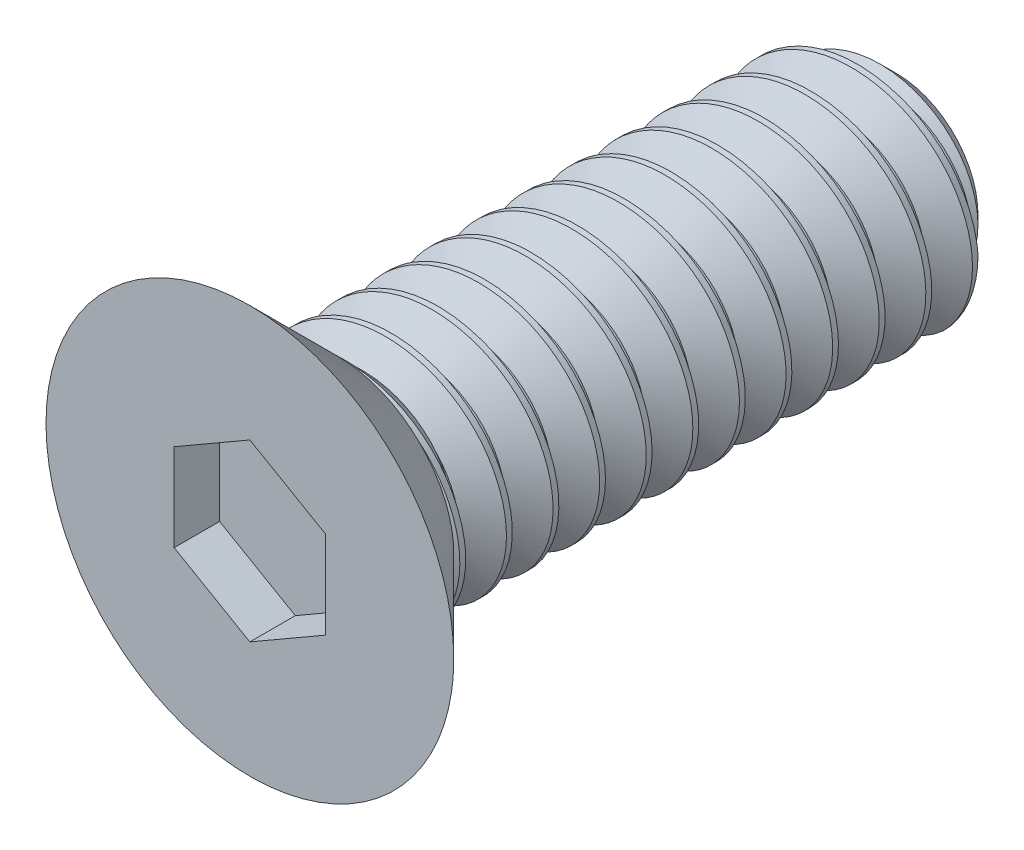
SolidWorks part; units mm, degrees
material "AISI Type 316L stainless steel"
ref_plane "Front" through (0, 0, 0) normal (0, 0, 1) x (1, 0, 0)
ref_plane "Top" through (0, 0, 0) normal (0, 1, 0) x (1, 0, 0)
ref_plane "Right" through (0, 0, 0) normal (1, 0, 0) x (0, 0, -1)
sketch "Sketch1" plane through (0, 0, 0) normal (1, 0, 0) x (0, 0, -1)
  line L0 (0, 2) -> (0.2, 2) construction
  line L1 (0.2, 2) -> (1.2, 1) construction
  line L2 (0, 1) -> (6, 1)
  line L3 (6, 1) -> (6, 0)
  line L4 (6, 0) -> (0, 0)
  line L5 (0, 0) -> (0, 2) construction
  line L6 (0, 2) -> (0, -2) construction
  line L7 (6, 1) -> (6, -1) construction
  line L8 (0, -2) -> (0.2, -2) construction
  line L9 (0.2, -2) -> (1.2, -1) construction
  line L11 (0, 1) -> (0, 0)
  line L12 (1.2, 1) -> (1.2, 0) construction
revolve "Revolve1" add sketch "Sketch1" angle 360 mid plane about L4
sketch "Sketch3" plane through (0, 0, -6) normal (0, 0, -1) x (-1, 0, 0)
  circle A0 centre (0, 0) radius 1
curve "Helix/Spiral1" pitch 0.4 height 6 radius 1 centre (0, 0, -6) axis (0, 0, 1) start towards (0, 1, 0)
sketch "Sketch2" plane through (0, 0, 0) normal (1, 0, 0) x (0, 0, -1)
  line L0 (6, 1) -> (6.35, 1)
  line L1 (6.35, 1) -> (6.2, 0.7402)
  line L2 (6.2, 0.7402) -> (6.15, 0.7402)
  line L3 (6.15, 0.7402) -> (6, 1)
  line L4 (6.075, 0.8701) -> (6.275, 0.8701) construction
  dimension "D1" = 60
  dimension "D2" = 0.05
  dimension "D3" = 0.2
chamfer "Chamfer1" distance 0.3 angle 45 1 edges at (0, 1, -6)
sweep "Cut-Sweep1" cut profiles "Sketch2" path "Helix/Spiral1" align with end faces yes
sketch "Sketch7" plane through (0, 0, 0) normal (1, 0, 0) x (0, 0, -1)
  line L0 (0, 2) -> (0.2, 2) construction
  line L1 (0.2, 2) -> (1.2, 1) construction
  line L2 (0, 2) -> (0.2, 2)
  line L3 (0.2, 2) -> (1.2, 1)
  line L4 (1.2, 1) -> (1.2, 0) construction
  line L5 (1.2, 1) -> (1.2, 0)
  line L7 (0, 0) -> (0, 2) construction
  line L8 (0, 0) -> (0, 2)
  line L9 (0, 0) -> (1.2, 0)
  line L10 (2.2, 0) -> (-2.2, 0) construction
revolve "Revolve2" add sketch "Sketch7" angle 360 mid plane about L9
ref_plane "Plane1" through (0, 0, -1.2) normal (0, 0, 1) x (1, 0, 0)
sketch "Sketch8" plane through (0, 0, -1.2) normal (0, 0, 1) x (1, 0, 0)
  circle A0 centre (0, 0) radius 1
extrude "Boss-Extrude1" add sketch "Sketch8" against normal through all draft 45
sketch "Sketch5" plane through (0, 0, 0) normal (0, 0, 1) x (1, 0, 0)
  line L1 (0.65, -0.3753) -> (0.65, 0.3753)
  line L2 (0.65, 0.3753) -> (0, 0.7506)
  line L3 (0, 0.7506) -> (-0.65, 0.3753)
  line L4 (-0.65, 0.3753) -> (-0.65, -0.3753)
  line L5 (-0.65, -0.3753) -> (0, -0.7506)
  line L6 (0, -0.7506) -> (0.65, -0.3753)
  circle A0 centre (0, 0) radius 0.65 construction
  dimension "Hex" = 1.3
extrude "Cut-Extrude2" cut sketch "Sketch5" against normal blind 0.84
sketch "Sketch6" plane through (0, 0, 0) normal (0, 0, 1) x (1, 0, 0)
  circle A0 centre (0, 0) radius 0.7506
extrude "Cut-Extrude3" cut sketch "Sketch6" against normal blind 0.84 draft 45
sketch "Sketch9" [suppressed] plane through (0, 0, -5.5) normal (0, 0, 1) x (1, 0, 0)
  circle A1 centre (0, 0) radius 5
  circle A2 centre (0, 0) radius 5
  point P0 (0, 5)
  dimension "D1" = 0
extrude "Boss-Extrude2" [suppressed] add sketch "Sketch9" against normal offset from surface (18.5 mm away) 26 up to face at (0, 0.7, -6)
fillet "Fillet1" [suppressed] radius 0.2
sketch "Sketch10" plane through (0, 0, 0) normal (1, 0, 0) x (0, 0, -1)
  line L0 (6, 1) -> (6, -1) construction
  point P0 (5.4, -1)
  dimension "D1" = 0.6
sketch "Sketch11" plane through (0, 0, 0) normal (1, 0, 0) x (0, 0, -1)
  line L1 (0, 0) -> (0.45, 0)
  line L2 (0, 0) -> (0, 2)
  line L3 (0, 2) -> (0.45, 2)
  line L4 (0.45, 0) -> (0.45, 2)
  point P5 (0, 2)
  dimension "D1" = 0.45
revolve "Cut-Revolve1" cut sketch "Sketch11" angle 360 about L1
equation "\"D3@Helix/Spiral1\" = \"Lg@Sketch1\""
equation "\"D2@Sketch2\" = \"D4@Helix/Spiral1\" * .125"
equation "\"D3@Sketch2\" = \"D4@Helix/Spiral1\" * .5"
equation "\"D1@Chamfer1\" = \"D4@Helix/Spiral1\" * .75"
equation "\"D1@Cut-Extrude2\" = \"Head Ht@Sketch1\" * .7"
equation "\"D1@Sketch10\" = \"D4@Helix/Spiral1\" * 1.5"
equation "\"D1@Cut-Extrude3\" = \"D1@Cut-Extrude2\""
equation "\"D1@Fillet1\" = \"Dia@Sketch1\" * .1"
